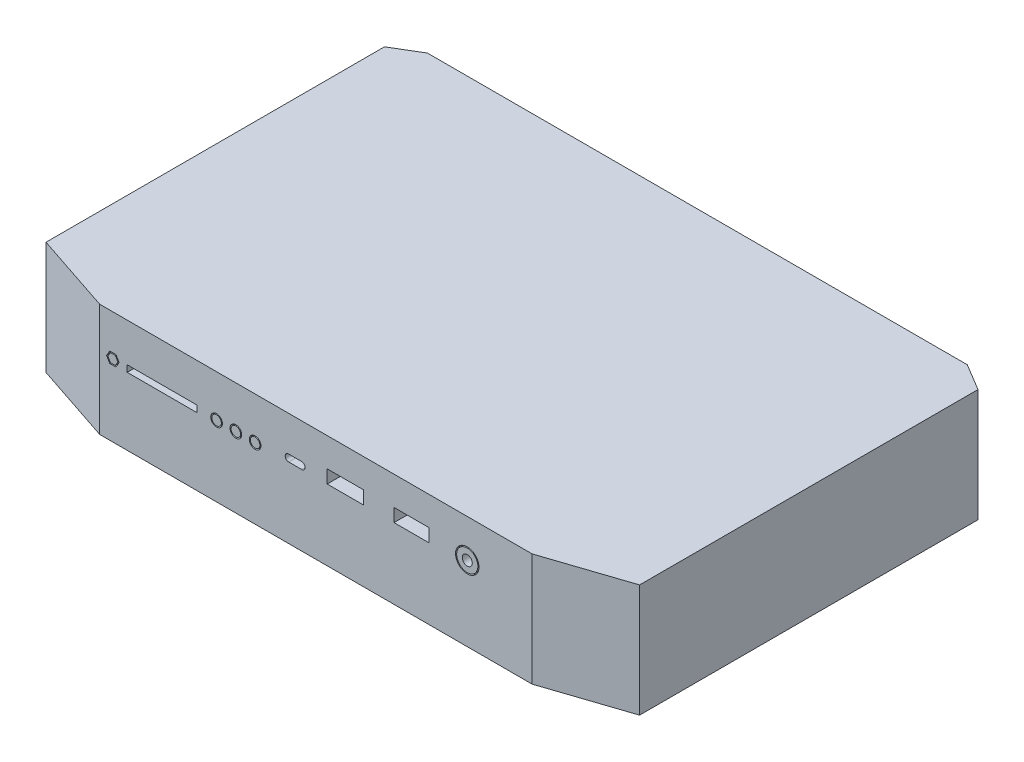
SolidWorks part; units mm, degrees
ref_plane "前视基准面" through (0, 0, 0) normal (0, 0, 1) x (1, 0, 0)
ref_plane "上视基准面" through (0, 0, 0) normal (0, 1, 0) x (1, 0, 0)
ref_plane "右视基准面" through (0, 0, 0) normal (1, 0, 0) x (0, 0, -1)
sketch "草图1" plane through (0, 0, 0) normal (0, 1, 0) x (1, 0, 0)
  line L1 (-110.5, 71) -> (110.5, 71)
  line L2 (-110.5, 71) -> (-110.5, -71)
  line L3 (-110.5, -71) -> (110.5, -71)
  line L4 (110.5, 71) -> (110.5, -71)
  line L5 (-110.5, 71) -> (110.5, -71) construction
  line L6 (-110.5, -71) -> (110.5, 71) construction
  point P0 (0, 0)
  dimension "D1" = 221
  dimension "D2" = 142
extrude "凸台-拉伸1" add sketch "草图1" along normal blind 42
ref_plane "基准面1" through (0, -3.3, 0) normal (0, 1, 0) x (1, 0, 0)
sketch "草图2" plane through (0, 0, 0) normal (0, -1, 0) x (1, 0, 0)
  line L0 (0, 71) -> (0, -71) construction
  line L1 (-110.5, 71) -> (110.5, 71) construction
  line L2 (110.5, -71) -> (-110.5, -71) construction
  point P6 (0, 46.4)
  point P7 (0, -45.7)
  dimension "D1" = 24.6
  dimension "D2" = 25.3
hole_wizard "M2 螺纹孔的螺纹孔钻头1" positions "草图3" profile "草图4" hole size "M2" standard "GB"
sketch "草图3" plane through (0, 0, 0) normal (0, -1, 0) x (-1, 0, 0)
  point P0 (0, 45.7)
  point P3 (0, -46.4)
sketch "草图4" plane through (0, 0, -45.7) normal (1, 0, 0) x (0, 0, -1)
  line L0 (0, 0) -> (0, 6.4807)
  line L1 (0, 6.4807) -> (0.8, 6)
  line L2 (0.8, 6) -> (0.8, 0.025)
  line L3 (0.8, 0.025) -> (0.825, 0)
  line L5 (0.825, 0) -> (0, 0)
  line L6 (-0.8, 0.025) -> (-0.825, 0) construction
  line L10 (0, 6.4807) -> (-0.8, 6) construction
  line L11 (0, -6.35) -> (0, 107.95) construction
  dimension "孔直径" = 1.6
  dimension "孔深度" = 6
  dimension "近端锥形沉头孔直径" = 1.65
  dimension "近端锥形沉头孔角度" = 90
  dimension "导头角度" = 118
sketch "草图5" plane through (0, 0, 0) normal (0, -1, 0) x (1, 0, 0)
  line L0 (-110.5, -65) -> (-100.5, -71)
  line L1 (-110.5, 61) -> (-80.5, 71)
  line L2 (-110.5, -71) -> (-110.5, 71) construction
  line L3 (0, 106.7608) -> (0, -114.1951) construction
  line L4 (110.5, -71) -> (110.5, 71)
  line L5 (110.5, 71) -> (-110.5, 71)
  line L6 (-110.5, 71) -> (-110.5, -71)
  line L7 (-110.5, -71) -> (110.5, -71)
  line L9 (80.5, 71) -> (-80.5, 71)
  line L10 (-110.5, 61) -> (-110.5, -65)
  line L11 (-100.5, -71) -> (100.5, -71)
  line L12 (110.5, 61) -> (110.5, -65)
  line L13 (110.5, 61) -> (80.5, 71)
  line L14 (110.5, -65) -> (100.5, -71)
  point P15 (0, -71)
  point P18 (0, 71)
  dimension "D2" = 6
  dimension "D3" = 10
  dimension "D4" = 30
  dimension "D5" = 10
  dimension "D1" = 0
extrude "切除-拉伸1" cut sketch "草图5" against normal blind 130 flip side to cut
sketch "草图7" plane through (0, 0, 0) normal (0, -1, 0) x (1, 0, 0)
  line L0 (100.5, -71) -> (-100.5, -71) construction
  line L1 (-85, 52) -> (85, 52)
  line L2 (-85, 52) -> (-85, -50) construction
  line L3 (-85, -50) -> (85, -50)
  line L4 (85, 52) -> (85, -50) construction
  line L5 (-85, 52) -> (85, -50) construction
  line L6 (-85, -50) -> (85, 52) construction
  line L7 (-81.5, -57) -> (81.5, -57)
  line L8 (-81.5, 59) -> (81.5, 59)
  line L9 (110.5, 61) -> (110.5, -65) construction
  line L10 (0, 223.7585) -> (0, -105.7585) construction
  line L11 (81.5, 59) -> (85, 52)
  line L12 (81.5, -57) -> (85, -50)
  line L13 (-81.5, 59) -> (-85, 52)
  line L14 (-81.5, -57) -> (-85, -50)
  point P0 (0, 1)
  point P15 (0, 59)
  point P16 (0, -57)
  dimension "D1" = 170
  dimension "D2" = 102
  dimension "D3" = 21
  dimension "D4" = 29
  dimension "D5" = 7
  dimension "D6" = 7
sketch "草图8" plane through (0, -3.3, 0) normal (0, 1, 0) x (1, 0, 0)
  line L0 (-82.5, 51) -> (82.5, 51)
  line L1 (82.5, -53) -> (-82.5, -53)
  line L2 (0, -223.7585) -> (0, 105.7585) construction
  line L3 (0, 84.786) -> (0, -104.677) construction
  line L4 (-85, -52) -> (85, -52) construction
  line L5 (-85, 50) -> (85, 50) construction
  point P4 (0, -53)
  dimension "D1" = 165
  dimension "D2" = 1
  dimension "D3" = 1
sketch "草图10" plane through (0, 0, 0) normal (1, 0, 0) x (0, 0, -1)
  line L0 (50, 0) -> (51, -3.3)
  line L1 (57, 0) -> (50, 0) construction
  line L3 (84.786, -3.3) -> (-104.677, -3.3) construction
  line L4 (51, -3.3) -> (57, 0)
  line L5 (57, 0) -> (50, 0)
extrude "凸台-拉伸2" add sketch "草图10" along normal mid plane 244 separate body
ref_plane "基准面2" through (-68.0142, -41.2207, -34.0071) normal (-0.7863, -0.4766, -0.3932) x (-0.3362, -0.2038, 0.9195)
sketch "草图11" plane through (-68.0142, -41.2207, -34.0071) normal (-0.7863, -0.4766, -0.3932) x (-0.3362, -0.2038, 0.9195)
  line L0 (-25.0067, 42.2416) -> (-18.4812, 39.9377)
  line L5 (-18.4812, 39.9377) -> (-17.3936, 44.0556)
  line L6 (-17.3936, 44.0556) -> (-25.0067, 42.2416)
  point P0 (-20.0347, 41.8729)
extrude "切除-拉伸2" cut sketch "草图11" along direction (-1, 0, 0) on the side of the normal blind 244
mirror "镜向1" about plane through (0, 0, 0) normal (1, 0, 0) of "切除-拉伸2"
sketch "草图13" plane through (0, 0, -71) normal (0, 0, -1) x (-1, 0, 0)
  line L0 (133.3333, 400) -> (666.6667, 400) construction
  line L1 (187.6562, 478.2166) -> (503.6562, 478.2166) construction
  line L2 (100.5, 0) -> (110.5, 0) construction
  line L3 (110.5, 0) -> (110.5, 42) construction
  line L4 (110.5, 42) -> (100.5, 42) construction
  line L5 (-100.5, 0) -> (100.5, 0) construction
  line L6 (100.5, 42) -> (-100.5, 42) construction
  line L7 (-110.5, 42) -> (-110.5, 0) construction
  line L8 (-110.5, 0) -> (-100.5, 0) construction
  line L9 (-100.5, 42) -> (-110.5, 42) construction
  line L10 (100.5, 0) -> (110.5, 0) construction
  line L11 (110.5, 0) -> (110.5, 42) construction
  line L12 (110.5, 42) -> (100.5, 42) construction
  line L13 (-100.5, 0) -> (100.5, 0) construction
  line L14 (100.5, 42) -> (-100.5, 42) construction
  line L15 (-110.5, 42) -> (-110.5, 0) construction
  line L16 (-110.5, 0) -> (-100.5, 0) construction
  line L17 (-100.5, 42) -> (-110.5, 42) construction
  line L18 (-39.2043, -2.1678) -> (276.7957, -2.1678) construction
  line L19 (9.7129, 29.787) -> (14.9469, 29.787) construction
  line L20 (-70.5612, 34.9711) -> (-54.123, 34.9711)
  line L21 (-70.5612, 34.9711) -> (-70.5612, 25.0354)
  line L22 (-70.5612, 25.0354) -> (-54.123, 25.0354)
  line L23 (-54.123, 34.9711) -> (-54.123, 25.0354)
  line L40 (9.7129, 31.115) -> (14.9469, 31.115)
  line L41 (9.7129, 28.459) -> (14.9469, 28.459)
  line L42 (25.3861, 32.9228) -> (39.4578, 32.9228)
  line L43 (39.4578, 32.9228) -> (39.4578, 30.3506)
  line L44 (39.4578, 30.3506) -> (37.3773, 28.2701)
  line L45 (37.3773, 28.2701) -> (27.4666, 28.2701)
  line L46 (27.4666, 28.2701) -> (25.3861, 30.3506)
  line L47 (25.3861, 30.3506) -> (25.3861, 32.9228)
  line L48 (32.422, 39.3156) -> (32.422, 23.9578) construction
  line L49 (48.0926, 33.6948) -> (48.0926, 29.787)
  line L50 (48.0926, 29.787) -> (50.0875, 27.8656)
  line L51 (50.0875, 27.8656) -> (54.8719, 27.8656)
  line L52 (54.8719, 27.8656) -> (56.8668, 29.787)
  line L53 (56.8668, 29.787) -> (56.8668, 33.6948)
  line L54 (56.8668, 33.6948) -> (48.0926, 33.6948)
  line L55 (-45.9528, 32.1073) -> (-6.175, 32.1073)
  line L56 (-45.9528, 37.191) -> (-6.175, 37.191)
  line L57 (-45.9528, 37.191) -> (-45.9528, 22.8317)
  line L58 (-45.9528, 22.8317) -> (-6.175, 22.8317)
  line L59 (-6.175, 37.191) -> (-6.175, 22.8317)
  line L60 (-6.175, 27.808) -> (-45.9528, 27.808)
  line L61 (-33.3773, 22.8317) -> (-33.3773, 37.191)
  line L62 (-19.018, 37.191) -> (-19.018, 22.8317)
  line L63 (52.4797, 38.1201) -> (52.4797, 24.3752) construction
  line L64 (-100.5, 42) -> (-100.5, 0) construction
  circle A0 centre (-81.4461, 29.135) radius 2.1366
  arc A1 (9.7129, 31.115) -> (9.7129, 28.459) centre (9.7129, 29.787) ccw
  arc A2 (14.9469, 28.459) -> (14.9469, 31.115) centre (14.9469, 29.787) ccw
  circle A3 centre (79.4018, 30.8271) radius 4.3827
  point P32 (32.422, 32.9228)
  point P35 (52.4797, 33.6948)
  point P38 (12.3299, 29.787)
  dimension "D1" = 8.7654
  dimension "D2" = 4.2732
  dimension "D3" = 1.328
  dimension "D4" = 19.0539
  dimension "D5" = 29.9388
  dimension "D6" = 46.377
  dimension "D7" = 54.5472
  dimension "D8" = 67.1227
  dimension "D9" = 81.482
  dimension "D10" = 94.325
  dimension "D11" = 110.2129
  dimension "D12" = 112.8299
  dimension "D13" = 125.8861
  dimension "D14" = 127.9666
  dimension "D15" = 132.922
  dimension "D16" = 148.5926
  dimension "D17" = 150.5875
  dimension "D18" = 152.9797
  dimension "D19" = 22.8317
  dimension "D20" = 25.0354
  dimension "D21" = 27.808
  dimension "D22" = 27.8656
  dimension "D23" = 28.2701
  dimension "D24" = 179.9018
  dimension "D25" = 29.135
  dimension "D26" = 29.787
  dimension "D28" = 30.8271
  dimension "D29" = 32.1073
  dimension "D30" = 32.9228
  dimension "D31" = 33.6948
  dimension "D32" = 34.9711
  dimension "D33" = 37.191
  dimension "D34" = 400
  dimension "D35" = 478.2166
  dimension "D36" = 2.1678
extrude "切除-拉伸3" cut sketch "草图13" against normal blind 5 contours A0 | L58 L61 L60 L57 | L55 L61 L56 L57 | L56 L62 L55 L59 | L60 L62 L58 L59 | L41 A2 L40 A1 | L53 L54 L49 L50 L51 L52 | A3 | L22 L23 L20 L21 | L45 L46 L47 L42 L43 L44 region at (-12.3299, 29.787, -71) region at (-52.4797, 30.9644, -71) region at (39.665, 34.6491, -71) region at (39.665, 25.3199, -71) region at (12.5965, 34.6491, -71) region at (12.5965, 25.3199, -71) region at (81.4461, 29.135, -71) region at (-79.4018, 30.8271, -71)
sketch "草图14" plane through (0, 0, -71) normal (0, 0, -1) x (-1, 0, 0)
  circle A0 centre (-81.4461, 29.135) radius 2.1366 construction
  circle A1 centre (-81.4461, 29.135) radius 2.1366
  circle A2 centre (-81.4461, 29.135) radius 4.5
  dimension "D1" = 9
extrude "切除-拉伸4" cut sketch "草图14" against normal blind 2
sketch "草图15" plane through (0, 0, -71) normal (0, 0, -1) x (-1, 0, 0)
  line L0 (100.5, 0) -> (110.5, 0) construction
  line L1 (110.5, 0) -> (110.5, 42) construction
  line L2 (110.5, 42) -> (100.5, 42) construction
  line L3 (-110.5, 42) -> (-110.5, 0) construction
  line L4 (-110.5, 0) -> (-100.5, 0) construction
  line L5 (-100.5, 42) -> (-110.5, 42) construction
  line L6 (-100.5, 0) -> (100.5, 0) construction
  line L7 (100.5, 42) -> (-100.5, 42) construction
  line L8 (100.5, 0) -> (110.5, 0) construction
  line L9 (110.5, 0) -> (110.5, 42) construction
  line L10 (110.5, 42) -> (100.5, 42) construction
  line L11 (-110.5, 42) -> (-110.5, 0) construction
  line L12 (-110.5, 0) -> (-100.5, 0) construction
  line L13 (-100.5, 42) -> (-110.5, 42) construction
  line L14 (-100.5, 0) -> (100.5, 0) construction
  line L15 (100.5, 42) -> (-100.5, 42) construction
  line L16 (-267.4119, -1.943) -> (48.5881, -1.943) construction
  line L17 (0, 0) -> (0, 68.2635) construction
  line L18 (-99.1125, 18.8061) -> (-97.4119, 4.7012)
  line L19 (-97.4119, 4.7012) -> (0, 4.7012)
  line L20 (0, 4.7012) -> (0, 18.8061)
  line L21 (0, 18.8061) -> (-99.1125, 18.8061)
  line L22 (-93.2147, 24.4717) -> (-88.8107, -2.1396) construction
  line L23 (-75.3372, 10.747) -> (-74.4743, 26.5331) construction
  line L24 (-75.3372, 10.747) -> (-73.0688, 0.5778) construction
  line L25 (-50.7678, 11.7283) -> (-51.7986, 0.5778) construction
  line L26 (-50.7678, 11.7283) -> (-52.8293, 22.1291) construction
  line L27 (-33.9953, 24.4717) -> (-35.5178, 11.7283) construction
  line L28 (-35.5178, 11.7283) -> (-33.9953, 2.4518) construction
  line L29 (-26.9878, 22.1291) -> (-27.7173, 11.7283) construction
  line L30 (-27.7173, 11.7283) -> (-26.4991, 3.2951) construction
  line L31 (-10.1014, 20.6886) -> (-11.139, 10.747) construction
  line L32 (-11.139, 10.747) -> (-10.1014, 2.4518) construction
  line L33 (-102.0226, 14.3519) -> (4.5161, 14.3519) construction
  line L34 (3.6728, 8.5424) -> (-102.9596, 8.5424) construction
  line L35 (-35.5178, 11.7283) -> (-27.7173, 11.7283) construction
  line L36 (3.6728, 8.9424) -> (-102.9596, 8.9424)
  line L37 (-75.7396, 10.7138) -> (-74.8738, 26.5549)
  line L38 (-75.7396, 10.7138) -> (-73.4592, 0.4907)
  line L39 (-102.0226, 13.9519) -> (4.5161, 13.9519)
  line L40 (-93.6093, 24.4064) -> (-89.2053, -2.2049)
  line L41 (-51.1715, 11.7073) -> (-53.2216, 22.0514)
  line L42 (-51.1715, 11.7073) -> (-52.1969, 0.6146)
  line L43 (-34.3924, 24.5191) -> (-35.915, 11.7757)
  line L44 (-35.9125, 11.6635) -> (-34.39, 2.387)
  line L45 (-35.5178, 11.3283) -> (-27.7173, 11.3283)
  line L46 (-28.1131, 11.6711) -> (-26.895, 3.2379)
  line L47 (-27.3869, 22.1571) -> (-28.1163, 11.7562)
  line L48 (-10.4992, 20.7302) -> (-11.5416, 10.7429)
  line L49 (-11.5416, 10.7429) -> (-10.4983, 2.4021)
  line L50 (3.6728, 8.1424) -> (-102.9596, 8.1424)
  line L51 (-74.9348, 10.7803) -> (-74.0749, 26.5113)
  line L52 (-74.9348, 10.7803) -> (-72.6784, 0.6648)
  line L53 (-102.0226, 14.7519) -> (4.5161, 14.7519)
  line L54 (-92.82, 24.537) -> (-88.4161, -2.0743)
  line L55 (-50.3642, 11.7492) -> (-52.4369, 22.2069)
  line L56 (-50.3642, 11.7492) -> (-51.4003, 0.5409)
  line L57 (-33.5981, 24.4242) -> (-35.1206, 11.6808)
  line L58 (-35.1231, 11.793) -> (-33.6005, 2.5166)
  line L59 (-35.5178, 12.1283) -> (-27.7173, 12.1283)
  line L60 (-27.3214, 11.7854) -> (-26.1032, 3.3523)
  line L61 (-26.5888, 22.1011) -> (-27.3182, 11.7003)
  line L62 (-9.7035, 20.6471) -> (-10.7364, 10.7511)
  line L63 (-10.7364, 10.7511) -> (-9.7044, 2.5014)
  line L64 (-35.915, 11.7757) -> (-35.9125, 11.6635)
  dimension "D1" = 0.4
  dimension "D2" = 0.4
extrude "切除-拉伸6" cut sketch "草图15" against normal blind 7 contours L21 L54 L53 L37 | L39 L54 L36 L38 L37 | L18 L53 L40 L21 | L40 L39 L18 L36 | L40 L50 L18 L19 | L50 L54 L19 L38 | L50 L52 L19 L42 | L51 L52 L36 L42 L41 L39 | L51 L53 L41 L21 | L55 L53 L43 L21 | L64 L43 L39 L55 L56 L36 L44 | L50 L56 L19 L44 | L57 L59 L47 L39 | L21 L57 L53 L47 | L53 L57 L39 L47 | L21 L61 L53 L48 | L39 L61 L60 L36 L49 L48 | L50 L60 L19 L49 | L21 L62 L53 L20 | L62 L63 L36 L20 L39 | L50 L63 L19 L20 region at (95.6062, 16.7696, -71) region at (94.843, 11.4332, -71) region at (83.4732, 16.7977, -71) region at (94.1253, 6.4155, -71) region at (83.1348, 11.4667, -71) region at (63.3907, 16.7636, -71) region at (82.3014, 6.418, -71) region at (63.0731, 11.4471, -71) region at (43.3402, 16.8061, -71) region at (62.8122, 6.4358, -71) region at (43.1343, 11.4445, -71) region at (31.1387, 16.769, -71) region at (31.3679, 14.3515, -71) region at (42.9539, 6.4058, -71) region at (31.4924, 13.0381, -71) region at (18.9366, 16.7819, -71) region at (19.2811, 11.4595, -71) region at (5.0544, 16.7649, -71) region at (18.774, 6.423, -71) region at (5.2948, 11.44, -71) region at (5.0982, 6.4339, -71)
extrude "切除-拉伸7" cut sketch "草图15<4>" against normal blind 2 contours L50 L58 L19 L46 | L45 L58 L36 L46 | L36 L58 L50 L46 region at (31.3714, 10.1367, -71) region at (31.1254, 8.5425, -71) region at (30.7986, 6.4246, -71)
sketch "草图15<4>" plane through (0, 0, -71) normal (0, 0, -1) x (-1, 0, 0) same geometry as "草图15"
mirror "镜向2" about plane through (0, 0, 0) normal (1, 0, 0) of "切除-拉伸6", "切除-拉伸7"
sketch "草图16" plane through (0, 0, 71) normal (0, 0, 1) x (1, 0, 0)
  line L0 (80.5, 0) -> (110.5, 0) construction
  line L1 (110.5, 0) -> (110.5, 42) construction
  line L2 (110.5, 42) -> (80.5, 42) construction
  line L3 (-110.5, 42) -> (-110.5, 0) construction
  line L4 (-110.5, 0) -> (-80.5, 0) construction
  line L5 (-80.5, 42) -> (-110.5, 42) construction
  line L6 (-80.5, 0) -> (80.5, 0) construction
  line L7 (80.5, 42) -> (-80.5, 42) construction
  line L8 (80.5, 0) -> (110.5, 0)
  line L9 (110.5, 0) -> (110.5, 42)
  line L10 (110.5, 42) -> (80.5, 42)
  line L11 (-110.5, 42) -> (-110.5, 0)
  line L12 (-110.5, 0) -> (-80.5, 0)
  line L13 (-80.5, 42) -> (-110.5, 42)
  line L14 (-80.5, 0) -> (80.5, 0)
  line L15 (80.5, 42) -> (-80.5, 42)
  line L16 (-271.1112, -81.7514) -> (44.8888, -81.7514) construction
  line L17 (-10.167, 27.5989) -> (-5.2852, 27.5989) construction
  line L18 (-70.2718, 27.5989) -> (-44.2918, 27.5989)
  line L19 (-70.2718, 27.5989) -> (-70.2718, 25.1556)
  line L20 (-70.2718, 25.1556) -> (-44.2918, 25.1556)
  line L21 (-44.2918, 27.5989) -> (-44.2918, 25.1556)
  line L22 (4.1936, 31.274) -> (42.0809, 31.274)
  line L23 (4.1936, 31.274) -> (4.1936, 26.3773)
  line L24 (4.1936, 26.3773) -> (42.0809, 26.3773)
  line L25 (42.0809, 31.274) -> (42.0809, 26.3773)
  line L26 (17.6721, 31.274) -> (29.0718, 31.274)
  line L27 (17.6721, 31.274) -> (17.6721, 26.3773)
  line L28 (17.6721, 26.3773) -> (29.0718, 26.3773)
  line L29 (29.0718, 31.274) -> (29.0718, 26.3773)
  line L30 (-10.167, 28.8779) -> (-5.2852, 28.8779)
  line L31 (-10.167, 26.3198) -> (-5.2852, 26.3198)
  line L32 (-74.6713, 25.165) -> (-73.7371, 26.7831)
  line L33 (-74.4404, 24.765) -> (-73.2752, 26.7831)
  line L34 (-73.2752, 26.7831) -> (-74.4404, 28.8013)
  line L35 (-74.4404, 28.8013) -> (-76.7708, 28.8013)
  line L36 (-76.7708, 28.8013) -> (-77.9359, 26.7831)
  line L37 (-77.9359, 26.7831) -> (-76.7708, 24.765)
  line L38 (-76.7708, 24.765) -> (-74.4404, 24.765)
  line L39 (75.1487, -4.1744) -> (69.2389, -4.1744)
  line L40 (69.2389, -4.1744) -> (66.284, -9.2924)
  line L41 (66.284, -9.2924) -> (69.2389, -14.4105)
  line L42 (69.2389, -14.4105) -> (75.1487, -14.4105)
  line L43 (75.1487, -14.4105) -> (78.1037, -9.2924)
  line L44 (78.1037, -9.2924) -> (75.1487, -4.1744)
  line L45 (-73.7371, 26.7831) -> (-74.6713, 28.4013)
  line L46 (-74.6713, 28.4013) -> (-76.5398, 28.4013)
  line L47 (-76.5398, 28.4013) -> (-77.4741, 26.7831)
  line L48 (-77.4741, 26.7831) -> (-76.5398, 25.165)
  line L49 (-76.5398, 25.165) -> (-74.6713, 25.165)
  line L50 (-80.5, 42) -> (-80.5, 0) construction
  arc A0 (-10.167, 28.8779) -> (-10.167, 26.3198) centre (-10.167, 27.5989) ccw
  arc A1 (-5.2852, 26.3198) -> (-5.2852, 28.8779) centre (-5.2852, 27.5989) ccw
  circle A2 centre (-75.6056, 26.7831) radius 2.0182 construction
  circle A3 centre (72.1938, -9.2924) radius 5.1181 construction
  circle A4 centre (56.345, 27.8455) radius 1.8659
  circle A5 centre (-37.0024, 26.3198) radius 1.7733
  circle A6 centre (-29.8237, 26.3198) radius 1.7733
  circle A7 centre (-22.645, 26.3198) radius 1.7733
  circle A8 centre (56.345, 27.8455) radius 4.3631
  circle A9 centre (56.345, 27.8455) radius 3.9468
  circle A10 centre (-37.0024, 26.3198) radius 2.1733
  circle A11 centre (-29.8237, 26.3198) radius 2.1733
  circle A12 centre (-22.645, 26.3198) radius 2.1733
  point P24 (-7.7261, 27.5989)
  dimension "D3" = 10.2361
  dimension "D4" = 3.5465
  dimension "D5" = 2.5641
  dimension "D6" = 3.7292
  dimension "D7" = 10.2282
  dimension "D8" = 3.7317
  dimension "D9" = 7.8935
  dimension "D10" = 8.7261
  dimension "D11" = 1.2791
  dimension "D12" = 36.2082
  dimension "D13" = 43.4976
  dimension "D14" = 50.6763
  dimension "D15" = 70.333
  dimension "D16" = 72.7739
  dimension "D17" = 84.6936
  dimension "D18" = 98.1721
  dimension "D19" = 109.5718
  dimension "D20" = 122.5809
  dimension "D21" = 136.845
  dimension "D22" = 146.784
  dimension "D23" = 14.4105
  dimension "D24" = 24.765
  dimension "D25" = 25.1556
  dimension "D26" = 26.3773
  dimension "D27" = 27.5989
  dimension "D28" = 27.8455
  dimension "D29" = 31.274
  dimension "D30" = 0.4
  dimension "D1" = 0.4
  dimension "D2" = 3
extrude "切除-拉伸8" cut sketch "草图16" against normal blind 7 contours A4 | L22 L29 L24 L25 | L27 L22 L23 L24 | L31 A1 L30 A0 | L21 L18 L19 L20 region at (-57.2818, 26.3773, 71) region at (10.9328, 28.8256, 71) region at (35.5763, 28.8256, 71) region at (-7.7261, 27.5989, 71) region at (56.345, 27.8455, 71)
extrude "切除-拉伸9" cut sketch "草图16<3>" against normal blind 1 contours A10 A5 | A11 A6 | A12 A7 | L37 L38 L33 L34 L35 L36 L49 L48 L47 L46 L45 L32 | A8 A9 | L43 L44 L39 L40 L41 L42 region at (-75.6056, 24.8266, 71) region at (72.1938, -9.2924, 71) region at (52.1054, 27.8455, 71) region at (-39.1142, 26.3198, 71) region at (-31.9355, 26.3198, 71) region at (-24.7568, 26.3198, 71)
sketch "草图16<3>" plane through (0, 0, 71) normal (0, 0, 1) x (1, 0, 0) same geometry as "草图16"
ref_plane "基准面3" through (0, 0, 1) normal (0, 0, -1) x (-1, 0, 0)
mirror "镜向4" about plane through (0, 0, 1) normal (0, 0, -1) of bodies 106
